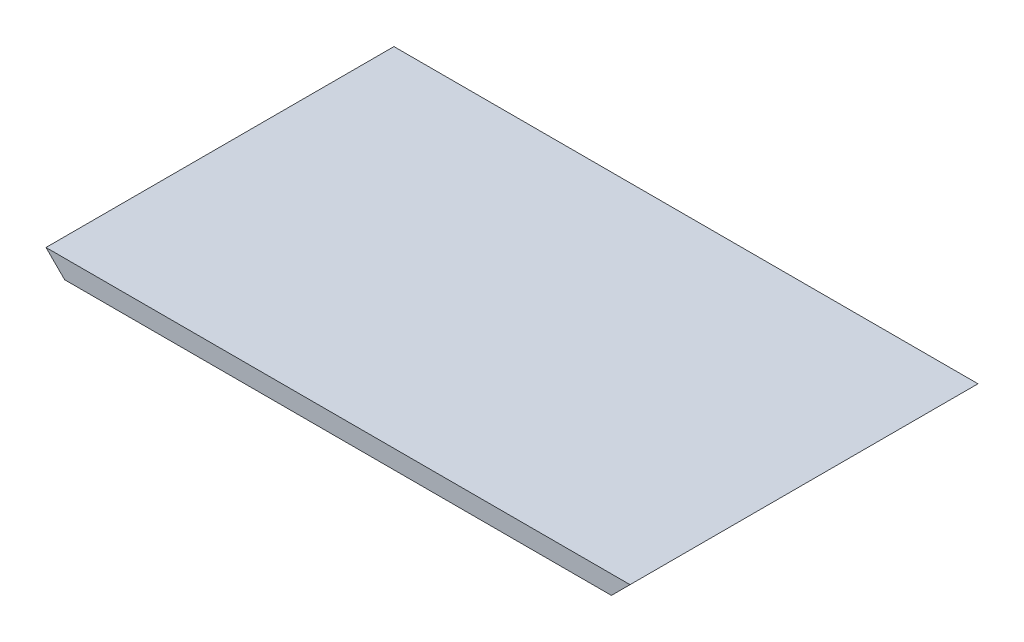
SolidWorks part; units mm, degrees
ref_plane "Front Plane" through (0, 0, 0) normal (0, 0, 1) x (1, 0, 0)
ref_plane "Top Plane" through (0, 0, 0) normal (0, 1, 0) x (1, 0, 0)
ref_plane "Right Plane" through (0, 0, 0) normal (1, 0, 0) x (0, 0, -1)
sketch "Sketch1" plane through (0, 0, 0) normal (0, 1, 0) x (1, 0, 0)
  line L1 (298.45, 177.8) -> (-298.45, 177.8)
  line L2 (298.45, 177.8) -> (298.45, -177.8)
  line L3 (298.45, -177.8) -> (-298.45, -177.8)
  line L4 (-298.45, 177.8) -> (-298.45, -177.8)
  line L5 (298.45, 177.8) -> (-298.45, -177.8) construction
  line L6 (298.45, -177.8) -> (-298.45, 177.8) construction
  point P0 (0, 0)
  dimension "D1" = 596.9
  dimension "D2" = 355.6
extrude "Boss-Extrude1" add sketch "Sketch1" along normal mid plane 19.05
chamfer "Chamfer1" distance 19.05 angle 45 2 edges at (298.45, -9.525, 0) (-298.45, -9.525, 0)
